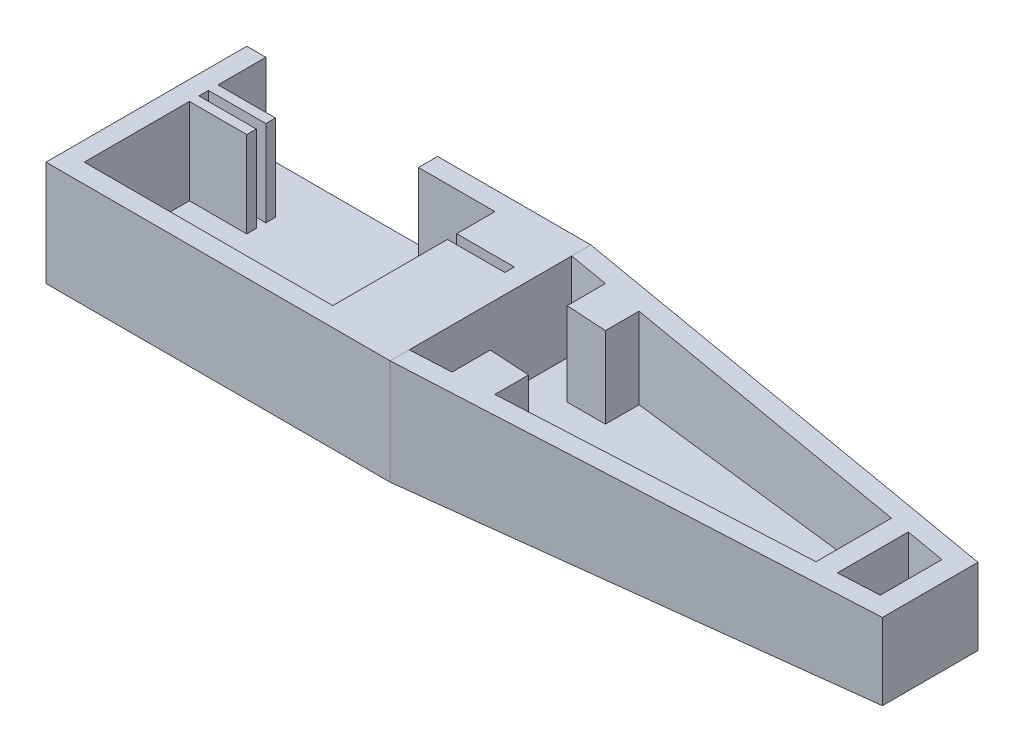
SolidWorks part; units mm, degrees
ref_plane "Front Plane" through (0, 0, 0) normal (0, 0, 1) x (1, 0, 0)
ref_plane "Top Plane" through (0, 0, 0) normal (0, 1, 0) x (1, 0, 0)
ref_plane "Right Plane" through (0, 0, 0) normal (1, 0, 0) x (0, 0, -1)
sketch "Sketch1" plane through (0, 0, 0) normal (0, 1, 0) x (1, 0, 0)
  line L0 (0, 0) -> (-40, 0) construction
  line L1 (0, 0) -> (40, 0) construction
  line L2 (-40, 0) -> (-40, 8.5) construction
  line L3 (-40, 0) -> (-40, -8.5) construction
  line L4 (-40, -8.5) -> (-14, -8.5) construction
  line L5 (-14, -8.5) -> (-8, -8.5) construction
  line L6 (-8, -8.5) -> (-6, -8.5) construction
  line L7 (-14, -8.5) -> (-14, 3.5) construction
  line L8 (-14, 3.5) -> (-8, 3.5) construction
  line L9 (-8, 3.5) -> (-8, 4.5) construction
  line L10 (-8, 4.5) -> (-14.0331, 4.5) construction
  line L11 (-14.0331, 4.5) -> (-14.0331, 8.5) construction
  line L12 (-6, -8.5) -> (-6, 8.5) construction
  line L13 (-6, 8.5) -> (-40, 8.5) construction
  line L14 (-40, 8.5) -> (-40, 10.5) construction
  line L15 (-40, 10.5) -> (-42, 10.5) construction
  line L16 (-40, -8.5) -> (-40, -10.5) construction
  line L17 (-40, -10.5) -> (-42, -10.5) construction
  line L18 (-6, -8.5) -> (-6, -10.5) construction
  line L19 (-6, 8.5) -> (-6, 10.5) construction
  line L20 (40, 0) -> (40, 5) construction
  line L21 (40, 0) -> (40, -5) construction
  line L22 (-42, 10.5) -> (-42, -10.5)
  line L23 (-42, -10.5) -> (-6, -10.5)
  line L27 (-6, 10.5) -> (-42, 10.5)
  line L28 (-40, 3.5) -> (-34, 3.5) construction
  line L29 (-40, -8.5) -> (-14, -8.5)
  line L30 (-14, -8.5) -> (-14, 3.5)
  line L31 (-14, 3.5) -> (-8, 3.5)
  line L32 (-8, 3.5) -> (-8, 4.5)
  line L33 (-8, 4.5) -> (-14.0331, 4.5)
  line L34 (-14.0331, 4.5) -> (-14.0331, 8.5)
  line L35 (-14.0331, 8.5) -> (-22.0331, 8.5)
  line L36 (-22.0331, 8.5) -> (-22.0331, 10.5)
  line L37 (-34, 3.5) -> (-34, 4.5) construction
  line L38 (-34, 4.5) -> (-40, 4.5) construction
  line L39 (-40, 10.5) -> (-40, 5.5)
  line L40 (-40, 5.5) -> (-34, 5.5)
  line L41 (-34, 5.5) -> (-34, 4.5)
  line L42 (-34, 4.5) -> (-40, 4.5)
  line L43 (-40, 4.5) -> (-40, 3.5)
  line L44 (-40, 3.5) -> (-34, 3.5)
  line L45 (-34, 3.5) -> (-34, 2.5)
  line L46 (-34, 2.5) -> (-40, 2.5)
  line L47 (-40, 2.5) -> (-40, -8.5)
  line L48 (-6, 10.5) -> (40, 5)
  line L49 (40, 5) -> (40, -5)
  line L50 (40, -5) -> (-6, -10.5)
  line L51 (17, 7.75) -> (16.7626, 5.7641) construction
  line L52 (16.7626, 5.7641) -> (40, 2.9858) construction
  line L53 (40, 2.9858) -> (38, 2.9858) construction
  line L54 (38, 2.9858) -> (38, 5.2391) construction
  line L55 (38, 2.9858) -> (38, -5.2391) construction
  line L56 (17, -7.75) -> (16.7626, -5.7641) construction
  line L57 (16.7626, -5.7641) -> (38, -3.2249) construction
  line L58 (-6, 8.5) -> (38, 3.2249)
  line L59 (38, 3.2249) -> (38, -3.2249)
  line L60 (38, -3.2249) -> (-6, -8.5)
  line L61 (-6, -8.5) -> (-6, 8.5)
  line L62 (38, 3.2249) -> (34, 3.2249) construction
  line L63 (-2, -8.0204) -> (-2, -4.0204) construction
  line L64 (34, 3.2249) -> (34, -3.2249) construction
  line L65 (-2, 8.0204) -> (-2, 4.0204) construction
  line L66 (-2, -8.0204) -> (-2, -4.0204)
  line L67 (-2, -4.0204) -> (2, -4.0204)
  line L68 (2, -4.0204) -> (2, -7.5409)
  line L69 (-2, 8.0204) -> (-2, 4.0204)
  line L70 (-2, 4.0204) -> (2, 4.0204)
  line L71 (2, 4.0204) -> (2, 7.5409)
  line L72 (34, -3.2249) -> (38, -3.2249) construction
  line L73 (34, 3.7044) -> (34, -3.7044)
  line L74 (34, 3.2249) -> (32, 3.2249) construction
  line L75 (32, 3.9442) -> (32, -3.9442)
extrude "Boss-Extrude1" add sketch "Sketch1" along normal blind 2 contours L46 L47 L29 L30 L31 L32 L33 L34 L35 L36 L27 L39 L40 L41 L42 L43 L44 L45 | L50 L49 L48 L27 L36 L35 L34 L33 L32 L31 L30 L29 L47 L46 L45 L44 L43 L42 L41 L40 L39 L22 L23 L60 L61 L58 L59 | L70 L71 L58 L69 | L75 L58 L71 L70 L69 L61 L60 L66 L67 L68 | L58 L75 L60 L73 | L68 L67 L66 L60 | L58 L73 L60 L59 region at (-41, 0, -9.6535) region at (-26.8517, 0, -0.6709) region at (11.4099, 0, 0) region at (-0.0425, 0, -5.9031) region at (-0.0425, 0, 5.9031) region at (32.9896, 0, 0) region at (35.9539, 0, 0)
extrude "Boss-Extrude2" add sketch "Sketch1<5>" along normal blind 11 contours L50 L49 L48 L27 L36 L35 L34 L33 L32 L31 L30 L29 L47 L46 L45 L44 L43 L42 L41 L40 L39 L22 L23 L60 L61 L58 L59 | L70 L71 L58 L69 | L68 L67 L66 L60 | L58 L75 L60 L73 region at (-41, 0, -9.6535) region at (-0.0425, 0, -5.9031) region at (-0.0425, 0, 5.9031) region at (32.9896, 0, 0)
sketch "Sketch1<5>" plane through (0, 0, 0) normal (0, 1, 0) x (1, 0, 0) same geometry as "Sketch1"
sketch "Sketch2" plane through (0, 0, 0) normal (0, 0, 1) x (1, 0, 0)
  line L0 (40, 0) -> (40, 8) construction
  line L1 (40, 11) -> (40, 0) construction
  line L2 (40, 8) -> (-6, 11) construction
  line L3 (-6, 11) -> (40, 11)
  line L4 (40, 11) -> (40, 8)
  line L5 (40, 8) -> (-6, 11)
extrude "Cut-Extrude1" cut sketch "Sketch2" against normal blind 11 and the other way blind 11
